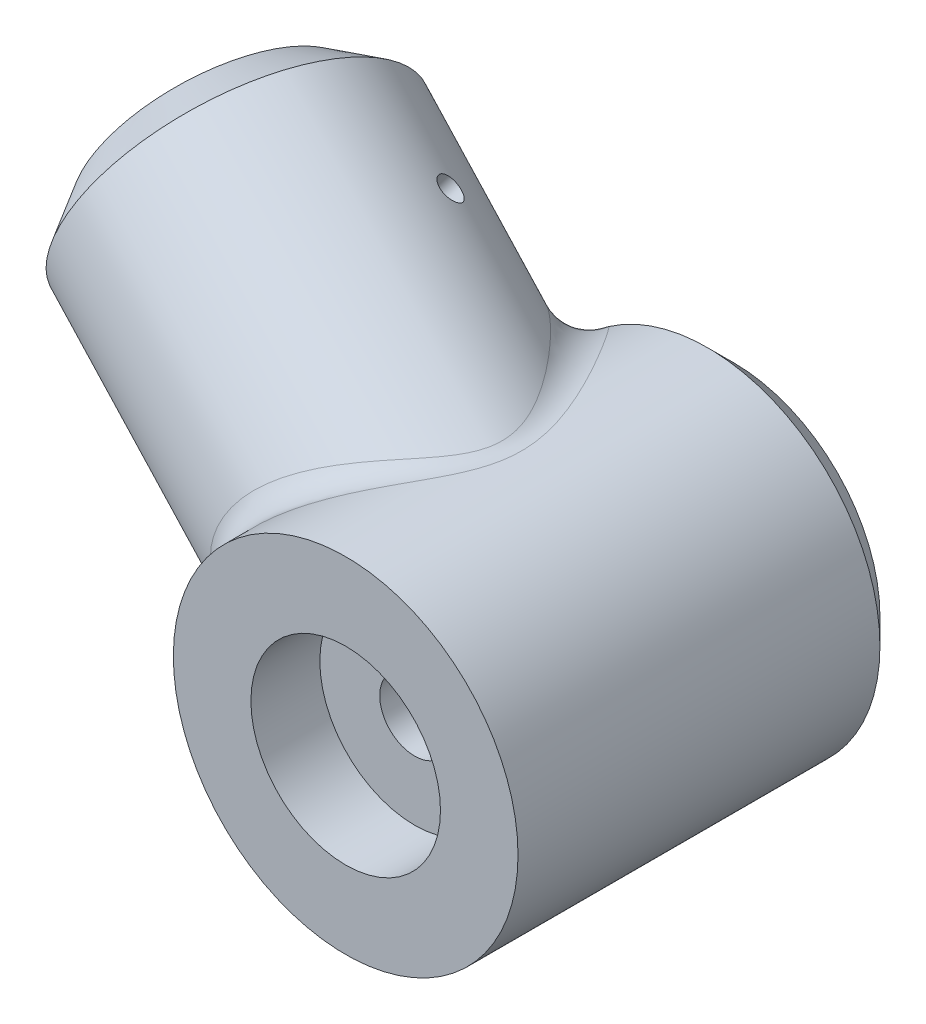
SolidWorks part; units mm, degrees
material "ABS"
ref_plane "Front Plane" through (0, 0, 0) normal (0, 0, 1) x (1, 0, 0)
ref_plane "Top Plane" through (0, 0, 0) normal (0, 1, 0) x (1, 0, 0)
ref_plane "Right Plane" through (0, 0, 0) normal (1, 0, 0) x (0, 0, -1)
sketch "Sketch1" plane through (0, 0, 0) normal (0, 0, 1) x (1, 0, 0)
  circle A0 centre (0, 0) radius 20
  dimension "D1" = 40
extrude "Boss-Extrude1" add sketch "Sketch1" along normal blind 45
sketch "Sketch2" plane through (0, 0, 45) normal (0, 0, 1) x (1, 0, 0)
  circle A0 centre (0, 0) radius 4.05
  dimension "D1" = 8.1
extrude "Cut-Extrude1" cut sketch "Sketch2" against normal blind 70
chamfer "Chamfer1" distance 3 angle 45 1 edges at (20, 0, 0)
sketch3d "3DSketch1"
  line L0 (-170, 80, -23) -> (-4.6324, 2.18, 25.6375)
  line L1 (-170, 80, -23) -> (0, 0, 27) construction
ref_plane "Plane1" through (-170, 80, -23) normal (0.8744, -0.4115, 0.2572) x (0.2327, -0.1095, -0.9664)
sketch "Sketch3" plane through (-170, 80, -23) normal (0.8744, -0.4115, 0.2572) x (0.2327, -0.1095, -0.9664)
  circle A0 centre (0, 0) radius 17.5
  circle A1 centre (0, 0) radius 12.9
  dimension "D1" = 35
  dimension "D2" = 25.8
extrude "Boss-Extrude2" add sketch "Sketch3" along normal blind 185
sketch "Sketch4" plane through (-170, 80, -23) normal (0.8744, -0.4115, 0.2572) x (0.2327, -0.1095, -0.9664)
  circle A0 centre (0, 0) radius 37.9547
extrude "Cut-Extrude3" cut sketch "Sketch4" along normal blind 140
chamfer "Chamfer2" distance 5 angle 45 1 edges at (-40.1346, 38.2277, 13.0041)
fillet "Fillet1" radius 4 1 edges at (-15.3519, 12.8187, 4.5158)
ref_plane "Plane2" through (-19.9307, -1.6638, 3) normal (-0.4852, -0.7469, 0.4547) x (-0.8714, 0.4563, -0.1803)
sketch "Sketch5" plane through (-19.9307, -1.6638, 3) normal (-0.4852, -0.7469, 0.4547) x (-0.8714, 0.4563, -0.1803)
  line L0 (3.5217, -21.005) -> (32.8727, -18.3846) construction
  line L1 (172.7165, -5.8999) -> (-15.6586, -22.7173) construction
  line L2 (31.7256, -5.5357) -> (34.0198, -31.2335) construction
  circle A0 centre (14.944, -19.9852) radius 1.5
  dimension "D1" = 3
  dimension "D2" = 18
extrude "Cut-Extrude4" cut sketch "Sketch5" against normal mid plane 80
sketch "Sketch6" plane through (0, 0, 45) normal (0, 0, 1) x (1, 0, 0)
  circle A0 centre (0, 0) radius 11
  dimension "D1" = 22
extrude "Cut-Extrude5" cut sketch "Sketch6" against normal blind 8
sketch "Sketch7" plane through (0, 0, 0) normal (0, 0, -1) x (-1, 0, 0)
  line L0 (-6.042, 0) -> (7.8621, 0) construction
  line L2 (-7.6788, 0) -> (-3.8394, -6.65)
  line L3 (-3.8394, -6.65) -> (3.8394, -6.65)
  line L4 (3.8394, -6.65) -> (7.6788, 0)
  line L5 (7.6788, 0) -> (3.8394, 6.65)
  line L6 (3.8394, 6.65) -> (-3.8394, 6.65)
  line L7 (-3.8394, 6.65) -> (-7.6788, 0)
  circle A0 centre (0, 0) radius 6.65 construction
  dimension "D1" = 13.3
extrude "Cut-Extrude6" cut sketch "Sketch7" against normal blind 7
ref_plane "Plane3" through (-41.1648, 19.3717, -12.1073) normal (0.8744, -0.4115, 0.2572) x (0.2327, -0.1095, -0.9664)
sketch "Sketch8" plane through (-41.1648, 19.3717, -12.1073) normal (0.8744, -0.4115, 0.2572) x (0.2327, -0.1095, -0.9664)
  circle A1 centre (-26.0919, 0) radius 12.9
  circle A2 centre (-26.0919, 0) radius 12.9
  dimension "D1" = 0
